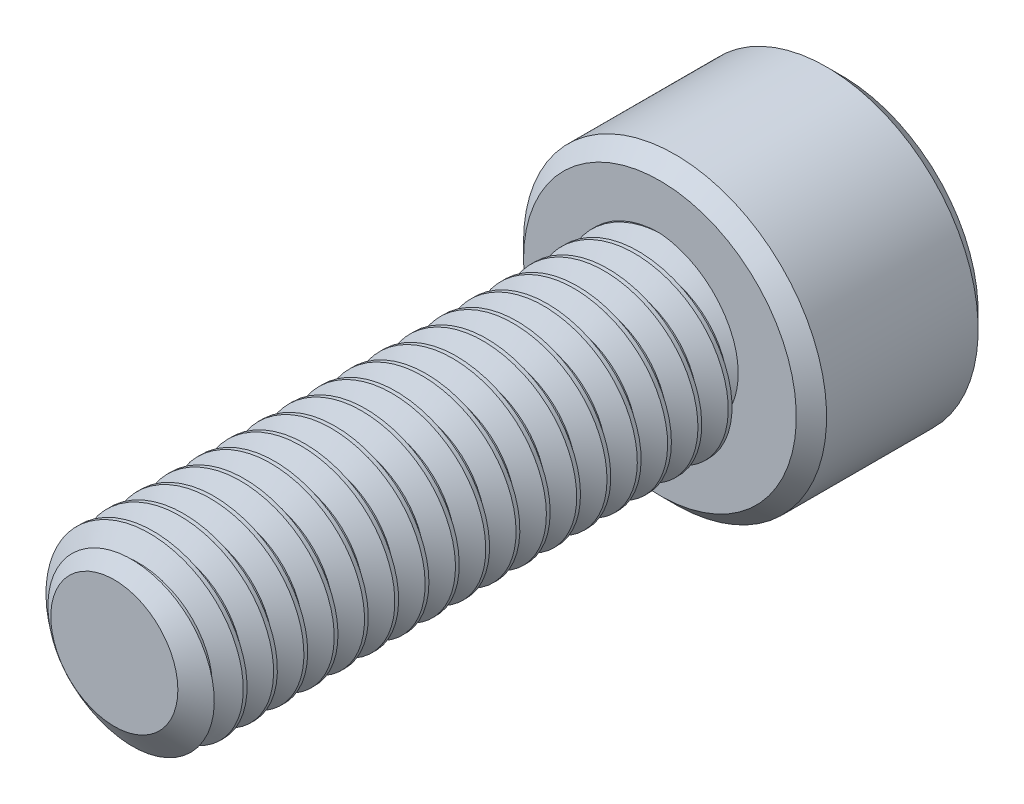
SolidWorks part; units mm, degrees
material "AISI 304"
ref_plane "Front Plane" through (0, 0, 0) normal (0, 0, 1) x (1, 0, 0)
ref_plane "Top Plane" through (0, 0, 0) normal (0, 1, 0) x (1, 0, 0)
ref_plane "Right Plane" through (0, 0, 0) normal (1, 0, 0) x (0, 0, -1)
sketch "Sketch1" plane through (0, 0, 0) normal (0, 0, 1) x (1, 0, 0)
  circle A0 centre (0, 0) radius 3
  dimension "OD" = 6
extrude "Extrude1" add sketch "Sketch1" against normal blind 18
sketch "Sketch2" plane through (0, 0, 0) normal (0, 0, 1) x (1, 0, 0)
  circle A0 centre (0, 0) radius 3 construction
  circle A1 centre (0, 0) radius 3
curve "Helix/Spiral1" pitch 1 height 19 turns 19 parameters "pitch"=1
sketch "Sketch3" plane through (0, 0, 0) normal (1, 0, 0) x (0, 0, -1)
  line L0 (-0.875, 3) -> (-0.5, 2.3505)
  line L1 (-0.5, 2.3505) -> (-0.375, 2.3505)
  line L2 (-0.375, 2.3505) -> (0, 3)
  line L3 (-0.875, 3) -> (0, 3)
  line L4 (-0.4375, 3) -> (-0.4375, 2.3505) construction
  line L5 (-0.6875, 2.6752) -> (-0.1875, 2.6752) construction
  line L6 (0, 3) -> (0, -3) construction
  dimension "D1" = 0.125
  dimension "D2" = 0.5
  dimension "D3" = 60
sweep "Cut-Sweep1" cut profiles "Sketch3" path "Helix/Spiral1"
sketch "Sketch4" plane through (0, 0, 0) normal (1, 0, 0) x (0, 0, -1)
  line L0 (0.6327, 3) -> (0, 2.0965)
  line L1 (0, 2.0965) -> (0, 3)
  line L2 (0.6327, 3) -> (0, 3)
  line L3 (-0.875, 3) -> (0, 3) construction
  line L4 (0, 0) -> (7.0209, 0) construction
  dimension "D1" = 55
  dimension "D2" = 0.254
revolve "Cut-Revolve1" cut sketch "Sketch4" angle 360 about L4
sketch "Sketch5" plane through (0, 0, 0) normal (1, 0, 0) x (0, 0, -1)
  line L0 (18, -2.3644) -> (18, 2.1406) construction
  line L1 (18, 3.127) -> (87.4327, 3.127)
  line L2 (18, 3.127) -> (18, 0)
  line L3 (18, 0) -> (87.3125, 0)
  line L4 (87.3125, 2.7968) -> (87.3125, 0)
  line L5 (87.4327, 3.127) -> (87.3125, 2.7968)
  line L6 (0, 0) -> (9.9695, 0) construction
  point P3 (87.3125, 3.127)
  point P10 (87.3125, 3.127)
  dimension "D1" = 0.3302
  dimension "Thread min" = 87.3125
  dimension "D2" = 0.127
  dimension "D3" = 20
revolve "partially thread" [suppressed] add sketch "Sketch5" angle 360 about L6
sketch "Sketch6" plane through (0, 0, -18) normal (0, 0, -1) x (-1, 0, 0)
  circle A0 centre (0, 0) radius 5
  dimension "head dia" = 10
extrude "Extrude2" add sketch "Sketch6" along normal blind 6
sketch "Sketch7" plane through (0, 0, -24) normal (0, 0, -1) x (-1, 0, 0)
  line L1 (0, 2.8868) -> (-2.5, 1.4434)
  line L2 (-2.5, 1.4434) -> (-2.5, -1.4434)
  line L3 (-2.5, -1.4434) -> (0, -2.8868)
  line L4 (0, -2.8868) -> (2.5, -1.4434)
  line L5 (2.5, -1.4434) -> (2.5, 1.4434)
  line L6 (2.5, 1.4434) -> (0, 2.8868)
  circle A0 centre (0, 0) radius 2.5 construction
  dimension "hex dia" = 5
extrude "Cut-Extrude1" cut sketch "Sketch7" against normal blind 3.75
sketch "Sketch8" plane through (0, 0, -24) normal (0, 0, -1) x (-1, 0, 0)
  circle A0 centre (0, 0) radius 2.8868
extrude "Cut-Extrude2" cut sketch "Sketch8" against normal through all draft 45
chamfer "Chamfer1" distance 0.5 angle 45 2 edges at (-5, 0, -24) (-5, 0, -18)
sketch "Sketch9" plane through (0, 0, 0) normal (1, 0, 0) x (0, 0, -1)
  line L0 (0, 3) -> (0, -3) construction
  line L1 (5.5, 3) -> (5.5, -3) construction
  dimension "D1" = 5.5
  dimension "D4" = 0.635
  dimension "D5" = 0.3302
equation "\"D3@Helix/Spiral1\" = \"screw length@Extrude1\"+\"pitch@Helix/Spiral1\""
equation "\"D1@Sketch3\" = \"pitch@Helix/Spiral1\"*.125"
equation "\"D2@Sketch3\" = \"pitch@Helix/Spiral1\"*.5"
equation "\"D1@Cut-Extrude1\" = \"hex dia@Sketch7\"*.75"
equation "\"D1@Chamfer1\" = \"head dia@Sketch6\"*.05"
equation "\"D1@Sketch9\" = \"pitch@Helix/Spiral1\"*5.5"
